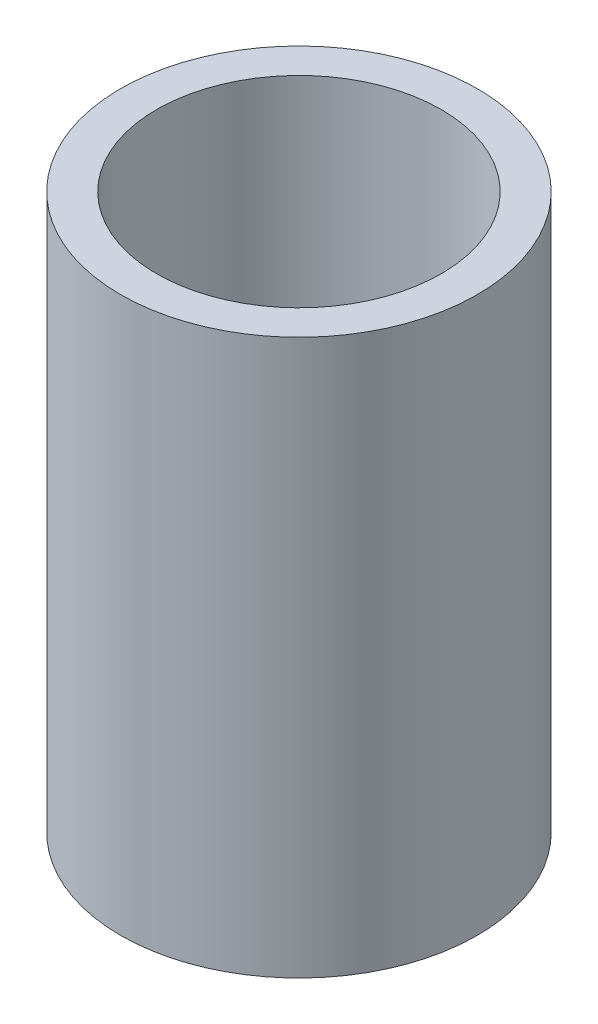
SolidWorks part; units mm, degrees
other "DetailItem1"
other "Markup1"
sketch "Sketch38" plane through (11.43, 31.75, 11.43) normal (0.7081, 0.685, 0.1713) x (0.2563, -0.0233, -0.9663)
ref_plane "Front Plane" through (0, 0, 0) normal (0, 0, 1) x (1, 0, 0)
ref_plane "Top Plane" through (0, 0, 0) normal (0, 1, 0) x (1, 0, 0)
ref_plane "Right Plane" through (0, 0, 0) normal (1, 0, 0) x (0, 0, -1)
sketch "Sketch1" plane through (0, 0, 0) normal (0, 1, 0) x (1, 0, 0)
  circle A0 centre (0, 0) radius 11.43
  dimension "D1" = 22.86
extrude "Boss-Extrude1" add sketch "Sketch1" along normal blind 16.51 contours A0
sketch "Sketch2" plane through (0, 0, 0) normal (0, -1, 0) x (1, 0, 0)
  circle A0 centre (0, 0) radius 9.144
  dimension "D1" = 18.288
extrude "Cut-Extrude1" cut sketch "Sketch2" against normal through all
thread "Thread1" pitch 1.5 method cut profile "Thread Profile1" start angle 0, offset 0, length 15.494, pitch 1.5, diameter 18.288
ref_plane "Plane1" through (9.144, 0, 0) normal (0, 0, 1) x (1, 0, 0)
sketch "Thread Profile1" plane through (9.144, 0, 0) normal (0, 0, 1) x (1, 0, 0)
  line L0 (0, 0) -> (0, 1.5) construction
  line L1 (0, 0) -> (0.8119, 0.4687)
  line L2 (0.8119, 0.4687) -> (0.8119, 0.6562)
  line L3 (0.8119, 0.6562) -> (0, 1.125)
  line L4 (0.8119, 0.5625) -> (0, 0.5625) construction
  line L11 (0, 0) -> (0, 1.125)
  point P2 (0, 0)
  dimension "Pitch" = 1.5
  dimension "Profile_Angle" = 60
  dimension "Profile_Land" = 0.1875
  dimension "Profile_Height" = 0.8119
ref_plane "Plane3" through (0, 19.05, 0) normal (0, 1, 0) x (1, 0, 0)
sketch "Sketch32" plane through (0, 16.51, 0) normal (0, 1, 0) x (1, 0, 0)
  circle A1 centre (0, 0) radius 11.43
  circle A2 centre (0, 0) radius 11.43
  circle A3 centre (0, 0) radius 9.1186
  dimension "D2" = 18.2372
  dimension "D1" = 0
extrude "Boss-Extrude5" add sketch "Sketch32" along normal blind 19.05
